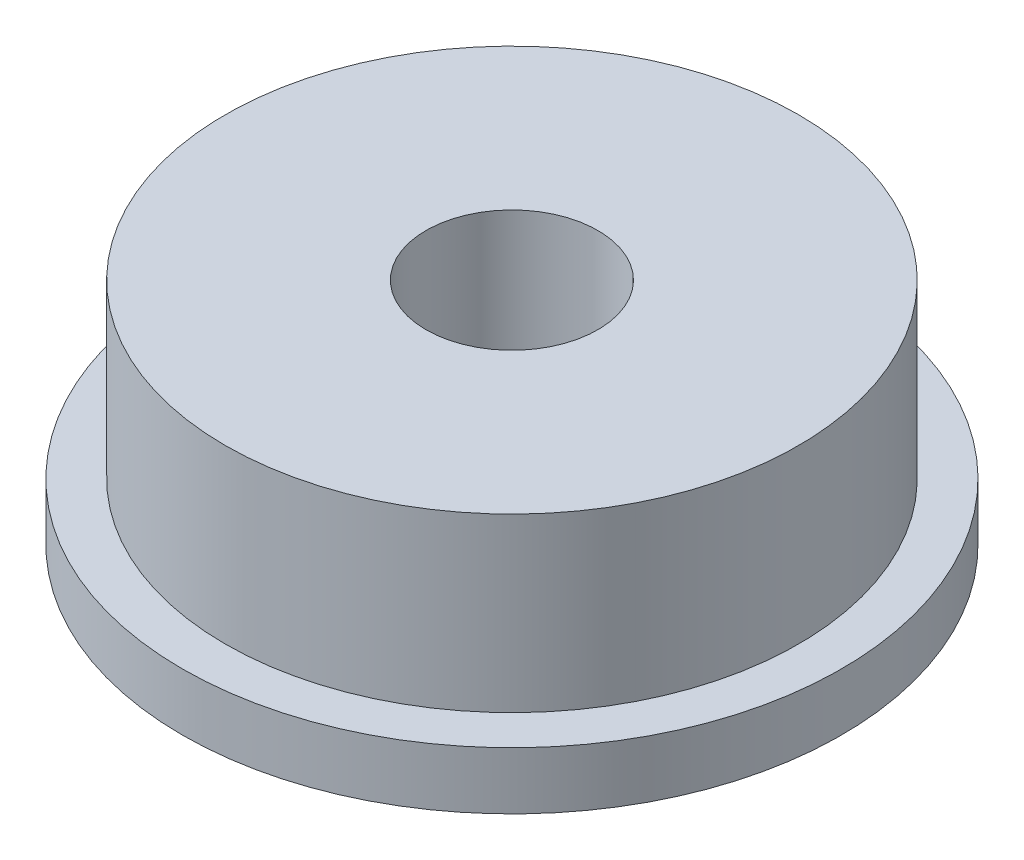
SolidWorks part; units mm, degrees
ref_plane "Front Plane" through (0, 0, 0) normal (0, 0, 1) x (1, 0, 0)
ref_plane "Top Plane" through (0, 0, 0) normal (0, 1, 0) x (1, 0, 0)
ref_plane "Right Plane" through (0, 0, 0) normal (1, 0, 0) x (0, 0, -1)
sketch "Sketch1" plane through (0, 0, 0) normal (0, 1, 0) x (1, 0, 0)
  circle A0 centre (0, 0) radius 1.5
  circle A1 centre (0, 0) radius 5
  circle A2 centre (0, 0) radius 5.75
  dimension "D1" = 3
  dimension "D2" = 10
  dimension "D3" = 11.5
extrude "Boss-Extrude1" add sketch "Sketch1" along normal blind 4 contours A1 A0 region at (-4.8586, 0, 0)
extrude "Boss-Extrude2" add sketch "Sketch1<3>" along normal blind 1 contours A2 A1 region at (-5.5874, 0, 0)
sketch "Sketch1<3>" plane through (0, 0, 0) normal (0, 1, 0) x (1, 0, 0) same geometry as "Sketch1"
